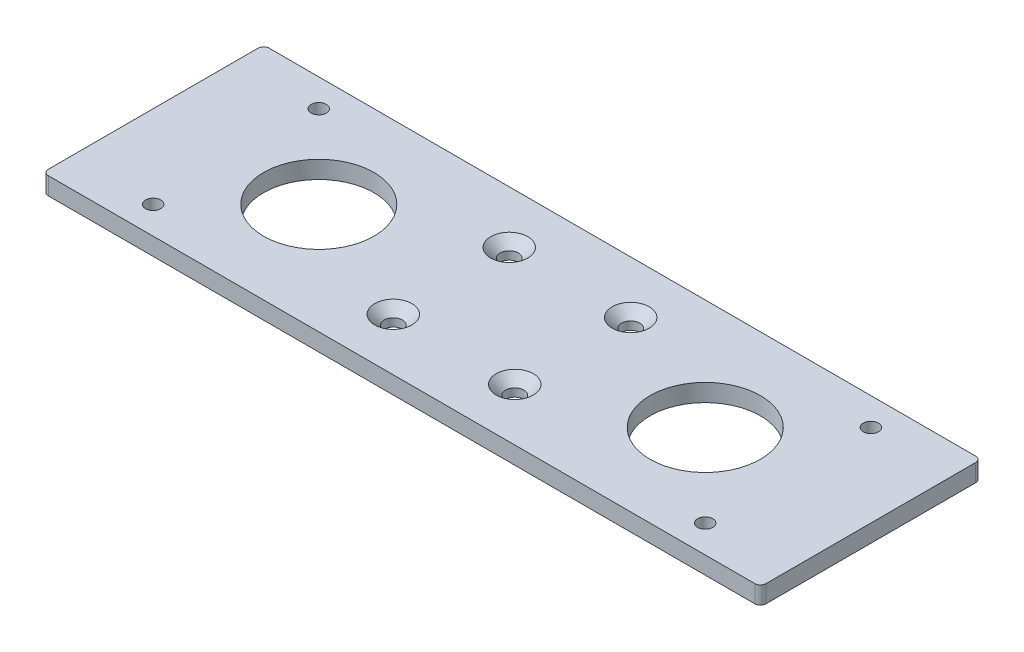
SolidWorks part; units mm, degrees
note: The reader was unsure of these and kept them because the rebuilt part matched: thickness of "Brida base1", "Chapa metálica1", "Chapa metálica2", "Chapa metálica3", "Chapa metálica4".
ref_plane "Alzado" through (0, 0, 0) normal (0, 0, 1) x (1, 0, 0)
ref_plane "Planta" through (0, 0, 0) normal (0, 1, 0) x (1, 0, 0)
ref_plane "Vista lateral" through (0, 0, 0) normal (1, 0, 0) x (0, 0, -1)
sketch "Croquis1" plane through (0, 0, 0) normal (0, 1, 0) x (1, 0, 0)
  line L1 (-149.7778, 34.4444) -> (110.2222, 34.4444)
  line L2 (-149.7778, 34.4444) -> (-149.7778, -45.5556)
  line L3 (-149.7778, -45.5556) -> (110.2222, -45.5556)
  line L4 (110.2222, 34.4444) -> (110.2222, -45.5556)
  dimension "D1" = 260
  dimension "D2" = 80
base flange "Brida base1" sketch "Croquis1" thickness 6.35 reverse thickness direction no parameters "D1"=10
fillet "Redondeo1" radius 2 4 edges at (-149.7778, -3.175, -34.4444) (110.2222, -3.175, -34.4444) (110.2222, -3.175, 45.5556) (-149.7778, -3.175, 45.5556)
hole_wizard "Taladro de margen para M51" positions "Croquis7" profile "Croquis6" hole size "M5" standard "Ansi Metric" end condition through all
sketch "Croquis7" plane through (0, 0, 0) normal (0, 1, 0) x (1, 0, 0)
  line L0 (-149.7778, 32.4444) -> (-149.7778, -43.5556) construction
  line L2 (-147.7778, -45.5556) -> (108.2222, -45.5556) construction
  line L7 (80.2222, -45.5556) -> (-149.7778, -45.5556) construction
  line L11 (-149.7778, -5.5556) -> (110.2222, -5.5556) construction
  line L12 (110.2222, -43.5556) -> (110.2222, 32.4444) construction
  point P0 (-119.7778, 24.4444)
  point P2 (-119.7778, -35.5556)
  point P4 (80.2222, -35.5556)
  point P6 (80.2222, 24.4444)
  dimension "D1" = 30
  dimension "D2" = 200
  dimension "D3" = 60
  dimension "D4" = 30
sketch "Croquis6" plane through (-119.7778, 0, -24.4444) normal (1, 0, 0) x (0, 0, 1)
  line L0 (0, 0) -> (0, 6.35)
  line L1 (0, 6.35) -> (2.75, 6.35)
  line L2 (2.75, 6.35) -> (2.75, 0)
  line L5 (2.75, 0) -> (0, 0)
  line L11 (0, -6.35) -> (0, 107.95) construction
  dimension "Diámetro de taladro hasta el siguiente" = 5.5
  dimension "Profundidad de taladro hasta el siguiente" = 6.35
sketch "Croquis8" plane through (0, 0, 0) normal (0, 1, 0) x (1, 0, 0)
  line L0 (-149.7778, -5.5556) -> (110.2222, -5.5556) construction
  line L1 (-149.7778, 32.4444) -> (-149.7778, -43.5556) construction
  line L2 (110.2222, -43.5556) -> (110.2222, 32.4444) construction
  line L3 (-19.7778, 34.4444) -> (-19.7778, -45.5556) construction
  line L4 (108.2222, 34.4444) -> (-147.7778, 34.4444) construction
  line L5 (-147.7778, -45.5556) -> (108.2222, -45.5556) construction
hole_wizard "Refrentado para tornillo tapón con cabeza plana de clavija de M61" positions "Croquis10" profile "Croquis9" countersink size "M6" standard "Ansi Metric" end condition through all
sketch "Croquis10" plane through (0, 0, 0) normal (0, 1, 0) x (1, 0, 0)
  line L0 (-19.7778, 34.4444) -> (-19.7778, -45.5556) construction
  line L1 (-149.7778, -5.5556) -> (110.2222, -5.5556) construction
  point P0 (-41.7778, 15.4444)
  point P2 (2.2222, 15.4444)
  point P4 (2.2222, -26.5556)
  point P6 (-41.7778, -26.5556)
  dimension "D1" = 42
  dimension "D2" = 44
  dimension "D3" = 22
  dimension "D4" = 21
sketch "Croquis9" plane through (-41.7778, 0, -15.4444) normal (1, 0, 0) x (0, 0, 1)
  line L0 (0, 0) -> (0, 6.35)
  line L1 (0, 6.35) -> (3.3, 6.35)
  line L2 (3.3, 6.35) -> (3.3, 3.42)
  line L3 (3.3, 3.42) -> (6.72, 0)
  line L5 (6.72, 0) -> (0, 0)
  line L6 (-3.3, 3.42) -> (-6.72, 0) construction
  line L11 (0, -6.35) -> (0, 107.95) construction
  dimension "Diámetro de taladro hasta el siguiente" = 6.6
  dimension "Profundidad de taladro hasta el siguiente" = 6.35
  dimension "Diámetro de avellanado cercano" = 13.44
  dimension "Ángulo de avellanado cercano" = 90
sketch "Croquis11" plane through (0, 0, 0) normal (0, 1, 0) x (1, 0, 0)
  line L0 (-149.7778, -5.5556) -> (110.2222, -5.5556) construction
  line L1 (-149.7778, 32.4444) -> (-149.7778, -43.5556) construction
  line L2 (110.2222, -43.5556) -> (110.2222, 32.4444) construction
  circle A0 centre (-89.7778, -5.5556) radius 20
  circle A1 centre (50.2222, -5.5556) radius 20
  dimension "D3" = 40
  dimension "D4" = 40
  dimension "D1" = 60
  dimension "D2" = 60
extrude "Cortar-Extruir1" cut sketch "Croquis11" against normal blind 10 contours A0 | A1 normal cut yes
sketch "Líneas de pliegue1" [suppressed] plane through (0, 0, 0) normal (0, 1, 0) x (1, 0, 0)
sketch "Cuadro delimitador1" [suppressed] plane through (0, 0, 0) normal (0, 1, 0) x (1, 0, 0)
sheet metal parameters "Chapa metálica1" thickness 6.35 parameters "D1"=10, "D7"=3
flat pattern "Chapa desplegada1" [suppressed]
sketch "Líneas de pliegue2" plane through (0, 0, 0) normal (0, 1, 0) x (1, 0, 0)
sketch3d "Cuadro delimitador2" [suppressed]
  line L0 (-149.7778, -85.5554, 0) -> (110.2222, -85.5556, 0) construction
  line L1 (-149.7777, 34.4444, 0) -> (110.2223, 34.4443, 0) construction
  line L2 (-149.7778, -85.5554, 0) -> (-149.7777, 34.4444, 0) construction
  line L3 (110.2222, -85.5556, 0) -> (110.2223, 34.4443, 0) construction
sheet metal parameters "Chapa metálica2" thickness 6.35 parameters "D1"=10
flat pattern "Chapa desplegada1"
sketch "Líneas de pliegue2" plane through (0, 0, 0) normal (0, 1, 0) x (1, 0, 0)
sketch3d "Cuadro delimitador2" [suppressed]
  line L0 (-149.7778, -85.5554, 0) -> (110.2222, -85.5556, 0) construction
  line L1 (-149.7777, 34.4444, 0) -> (110.2223, 34.4443, 0) construction
  line L2 (-149.7778, -85.5554, 0) -> (-149.7777, 34.4444, 0) construction
  line L3 (110.2222, -85.5556, 0) -> (110.2223, 34.4443, 0) construction
sheet metal parameters "Chapa metálica3" thickness 6.35 parameters "D1"=10
flat pattern "Chapa desplegada1"
sketch "Líneas de pliegue2" plane through (0, 0, 0) normal (0, 1, 0) x (1, 0, 0)
sketch3d "Cuadro delimitador2" [suppressed]
  line L0 (-149.7778, -45.5554, 0) -> (110.2222, -45.5556, 0) construction
  line L1 (-149.7777, 34.4444, 0) -> (110.2223, 34.4443, 0) construction
  line L2 (-149.7778, -45.5554, 0) -> (-149.7777, 34.4444, 0) construction
  line L3 (110.2222, -45.5556, 0) -> (110.2223, 34.4443, 0) construction
sheet metal parameters "Chapa metálica4" thickness 6.35 parameters "D1"=10
flat pattern "Chapa desplegada1"
sketch "Líneas de pliegue2" plane through (0, 0, 0) normal (0, 1, 0) x (1, 0, 0)
sketch3d "Cuadro delimitador2" [suppressed]
  line L0 (-149.7778, -45.5554, 0) -> (110.2222, -45.5556, 0) construction
  line L1 (-149.7777, 34.4444, 0) -> (110.2223, 34.4443, 0) construction
  line L2 (-149.7778, -45.5554, 0) -> (-149.7777, 34.4444, 0) construction
  line L3 (110.2222, -45.5556, 0) -> (110.2223, 34.4443, 0) construction
